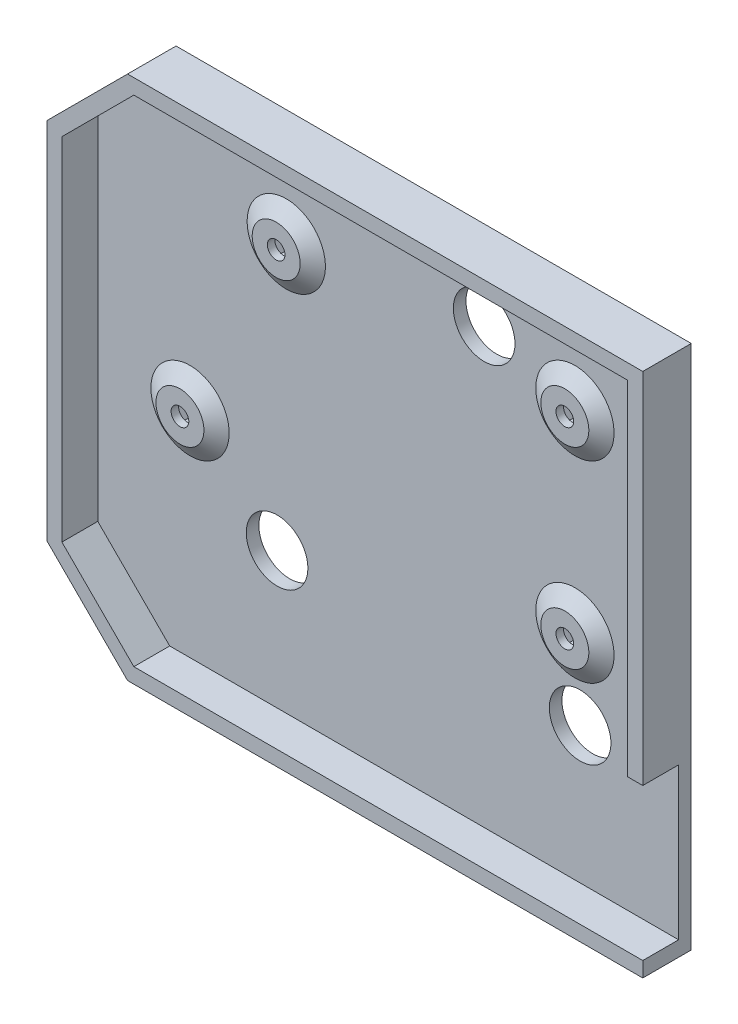
SolidWorks part; units mm, degrees
ref_plane "Plan de face" through (0, 0, 0) normal (0, 0, 1) x (1, 0, 0)
ref_plane "Plan de dessus" through (0, 0, 0) normal (0, 1, 0) x (1, 0, 0)
ref_plane "Plan de droite" through (0, 0, 0) normal (1, 0, 0) x (0, 0, -1)
sketch "Esquisse1" plane through (0, 0, 0) normal (0, 0, 1) x (1, 0, 0)
  line L0 (0, -85) -> (16, -101)
  line L4 (118, 3) -> (118, -101)
  line L5 (16, 3) -> (0, -13)
  line L7 (118, 3) -> (16, 3)
  line L8 (0, -13) -> (0, -85)
  line L9 (16, -101) -> (118, -101)
  dimension "D1" = 104
  dimension "D2" = 118
  dimension "D3" = 16
  dimension "D4" = 16
  dimension "D5" = 16
  dimension "D6" = 16
extrude "Boss.-Extru.1" add sketch "Esquisse1" along normal blind 2.5
sketch "Esquisse2" plane through (0, 0, 2.5) normal (0, 0, 1) x (1, 0, 0)
  line L0 (0, -13) -> (0, -85) construction
  line L1 (3, 0) -> (115, 0) construction
  line L2 (3, 0) -> (3, -98) construction
  line L3 (3, -98) -> (115, -98) construction
  line L4 (115, 0) -> (115, -98) construction
  line L5 (16, -101) -> (118, -101) construction
  line L6 (118, -101) -> (118, 3) construction
  line L7 (118, 3) -> (16, 3) construction
  line L9 (3, -83.7574) -> (17.2426, -98)
  line L10 (0, -85) -> (16, -101) construction
  line L11 (3, -14.2426) -> (17.2426, 0)
  line L12 (16, 3) -> (0, -13) construction
  line L13 (115, 0) -> (17.2426, 0)
  line L14 (3, -14.2426) -> (3, -83.7574)
  line L15 (17.2426, -98) -> (115, -98)
  line L16 (118, 3) -> (118, -101) construction
  line L17 (118, -101) -> (16, -101)
  line L18 (16, -101) -> (0, -85)
  line L19 (0, -85) -> (0, -13)
  line L20 (0, -13) -> (16, 3)
  line L21 (16, 3) -> (118, 3)
  line L30 (118, -2.5) -> (118, 3)
  line L31 (115, -98) -> (118, -98)
  line L32 (118, -98) -> (118, -101)
  line L33 (115, 0) -> (115, -68)
  line L34 (115, -68) -> (118, -68)
  line L35 (118, -68) -> (118, -2.5)
  point P24 (116.5, -98)
  dimension "D1" = 3
  dimension "D2" = 3
  dimension "D3" = 3
  dimension "D4" = 3
  dimension "D5" = 3
  dimension "D6" = 3
  dimension "D7" = 30
extrude "Boss.-Extru.2" add sketch "Esquisse2" along normal blind 7.1
sketch "Esquisse3" plane through (0, 0, 2.5) normal (0, 0, 1) x (1, 0, 0)
  line L0 (118, -98) -> (17.2426, -98) construction
  line L1 (17.2426, 0) -> (115, 0) construction
  line L2 (115, 0) -> (115, -68) construction
  line L3 (3, -83.7574) -> (3, -14.2426) construction
  circle A0 centre (98.5, -71) radius 6.1
  circle A1 centre (79.5, -12) radius 6.1
  circle A2 centre (38.5, -71) radius 6.1
  dimension "D1" = 27
  dimension "D2" = 27
  dimension "D3" = 12
  dimension "D4" = 16.5
  dimension "D5" = 35.5
  dimension "D6" = 35.5
extrude "Enlèv. mat.-Extru.1" cut sketch "Esquisse3" against normal blind 10
sketch "Esquisse4" plane through (0, 0, 2.5) normal (0, 0, 1) x (1, 0, 0)
  line L0 (115, 0) -> (115, -68) construction
  line L1 (17.2426, 0) -> (115, 0) construction
  point P0 (40.32, -17.53)
  point P1 (21.27, -55.63)
  point P2 (97.47, -55.63)
  point P3 (97.47, -17.53)
  point P4 (0, 0)
  point P5 (0, 0)
  dimension "D1" = 17.53
  dimension "D2" = 17.53
  dimension "D3" = 38.1
  dimension "D4" = 57.15
  dimension "D5" = 76.2
ref_axis "Axe1" through (97.47, -55.63, 2.5) along (0, 0, 1)
ref_axis "Axe2" through (21.27, -55.63, 2.5) along (0, 0, 1)
ref_axis "Axe3" through (40.32, -17.53, 2.5) along (0, 0, 1)
ref_axis "Axe4" through (97.47, -17.53, 2.5) along (0, 0, 1)
ref_plane "Plan1" through (0, -55.63, 0) normal (0, -1, 0) x (-1, 0, 0)
ref_plane "Plan2" through (0, -17.53, 0) normal (0, 1, 0) x (1, 0, 0)
sketch "Esquisse9" plane through (0, -55.63, 0) normal (0, -1, 0) x (-1, 0, 0)
  line L0 (-95.72, -2.5) -> (-89.72, -2.5)
  line L1 (-89.72, -2.5) -> (-92.72, -4.5)
  line L2 (-92.72, -4.5) -> (-95.72, -4.5)
  line L3 (-95.72, -4.5) -> (-95.72, -2.5)
  line L4 (-97.47, -2.5) -> (-97.47, -52.3606) construction
  point P0 (-98.5795, 0)
  dimension "D1" = 2
  dimension "D2" = 1.75
  dimension "D3" = 3
  dimension "D4" = 6
ref_point "Point1"
ref_point "Point2"
ref_point "Point3"
ref_point "Point4"
revolve "Révolution1" add sketch "Esquisse9" angle 360 about axis through (97.47, -55.63, 2.5) along (0, 0, 1)
sketch "Esquisse11" plane through (0, -55.63, 0) normal (0, -1, 0) x (-1, 0, 0)
  line L0 (-23.02, -2.5) -> (-29.02, -2.5)
  line L1 (-29.02, -2.5) -> (-26.02, -4.5)
  line L2 (-26.02, -4.5) -> (-23.02, -4.5)
  line L3 (-23.02, -4.5) -> (-23.02, -2.5)
  line L4 (-21.27, -2.5) -> (-21.27, -52.3606) construction
  dimension "D1" = 1.75
  dimension "D2" = 3
  dimension "D3" = 6
  dimension "D4" = 2
revolve "Révolution2" add sketch "Esquisse11" angle 360 about axis through (21.27, -55.63, 2.5) along (0, 0, 1)
sketch "Esquisse12" plane through (0, -17.53, 0) normal (0, 1, 0) x (1, 0, 0)
  line L0 (95.72, -2.5) -> (89.72, -2.5)
  line L1 (89.72, -2.5) -> (92.72, -4.5)
  line L2 (92.72, -4.5) -> (95.72, -4.5)
  line L3 (95.72, -4.5) -> (95.72, -2.5)
  line L4 (97.47, -2.5) -> (97.47, -52.3606) construction
  dimension "D1" = 1.75
  dimension "D2" = 2
  dimension "D3" = 3
  dimension "D4" = 6
revolve "Révolution3" add sketch "Esquisse12" angle 360 about axis through (97.47, -17.53, 2.5) along (0, 0, 1)
sketch "Esquisse13" plane through (0, -17.53, 0) normal (0, 1, 0) x (1, 0, 0)
  line L0 (42.07, -2.5) -> (48.07, -2.5)
  line L1 (48.07, -2.5) -> (45.07, -4.5)
  line L2 (45.07, -4.5) -> (42.07, -4.5)
  line L3 (42.07, -4.5) -> (42.07, -2.5)
  line L4 (40.32, -2.5) -> (40.32, -52.3606) construction
  dimension "D1" = 1.75
  dimension "D2" = 3
  dimension "D3" = 6
  dimension "D4" = 2
revolve "Révolution4" add sketch "Esquisse13" angle 360 about axis through (40.32, -17.53, 2.5) along (0, 0, 1)
hole_wizard "Dégagement M31" positions "Esquisse14" profile "Esquisse15" hole size "M3" standard "Ansi Metric" end condition up to next
sketch "Esquisse14" plane through (0, 0, 2.5) normal (0, 0, 1) x (1, 0, 0)
  point P0 (97.47, -55.63)
  point P3 (21.27, -55.63)
  point P6 (97.47, -17.53)
  point P9 (40.32, -17.53)
sketch "Esquisse15" plane through (97.47, -55.63, 2.5) normal (1, 0, 0) x (0, -1, 0)
  line L0 (0, 0) -> (0, 2.5)
  line L1 (0, 2.5) -> (1.8, 2.5)
  line L2 (1.8, 2.5) -> (1.8, 0)
  line L5 (1.8, 0) -> (0, 0)
  line L11 (0, -6.35) -> (0, 107.95) construction
  dimension "Diamètre du perçage jusqu'au prochain" = 3.6
  dimension "Profondeur du perçage jusqu'au prochain" = 2.5
ref_point "Point5"
ref_point "Point6"
ref_point "Point7"
ref_point "Point8"
sketch "Esquisse16" plane through (0, 0, 0) normal (0, 0, -1) x (-1, 0, 0)
  line L0 (-118, 3) -> (-16, 3) construction
  line L1 (-22.8288, -52.93) -> (-24.3877, -55.63)
  line L2 (-24.3877, -55.63) -> (-22.8288, -58.33)
  line L3 (-22.8288, -58.33) -> (-19.7112, -58.33)
  line L4 (-19.7112, -58.33) -> (-18.1523, -55.63)
  line L5 (-18.1523, -55.63) -> (-19.7112, -52.93)
  line L6 (-19.7112, -52.93) -> (-22.8288, -52.93)
  line L7 (-99.0288, -52.93) -> (-100.5877, -55.63)
  line L8 (-100.5877, -55.63) -> (-99.0288, -58.33)
  line L9 (-99.0288, -58.33) -> (-95.9112, -58.33)
  line L10 (-95.9112, -58.33) -> (-94.3523, -55.63)
  line L11 (-94.3523, -55.63) -> (-95.9112, -52.93)
  line L12 (-95.9112, -52.93) -> (-99.0288, -52.93)
  line L13 (-99.0288, -14.83) -> (-100.5877, -17.53)
  line L14 (-100.5877, -17.53) -> (-99.0288, -20.23)
  line L15 (-99.0288, -20.23) -> (-95.9112, -20.23)
  line L16 (-95.9112, -20.23) -> (-94.3523, -17.53)
  line L17 (-94.3523, -17.53) -> (-95.9112, -14.83)
  line L18 (-95.9112, -14.83) -> (-99.0288, -14.83)
  line L19 (-41.8788, -14.83) -> (-43.4377, -17.53)
  line L20 (-43.4377, -17.53) -> (-41.8788, -20.23)
  line L21 (-41.8788, -20.23) -> (-38.7612, -20.23)
  line L22 (-38.7612, -20.23) -> (-37.2023, -17.53)
  line L23 (-37.2023, -17.53) -> (-38.7612, -14.83)
  line L24 (-38.7612, -14.83) -> (-41.8788, -14.83)
  circle A0 centre (-21.27, -55.63) radius 2.7 construction
  circle A1 centre (-97.47, -55.63) radius 2.7 construction
  circle A2 centre (-97.47, -17.53) radius 2.7 construction
  circle A3 centre (-40.32, -17.53) radius 2.7 construction
  dimension "D1" = 5.4
  dimension "D2" = 5.4
  dimension "D3" = 5.4
  dimension "D4" = 5.4
extrude "Enlèv. mat.-Extru.2" cut sketch "Esquisse16" against normal blind 3
